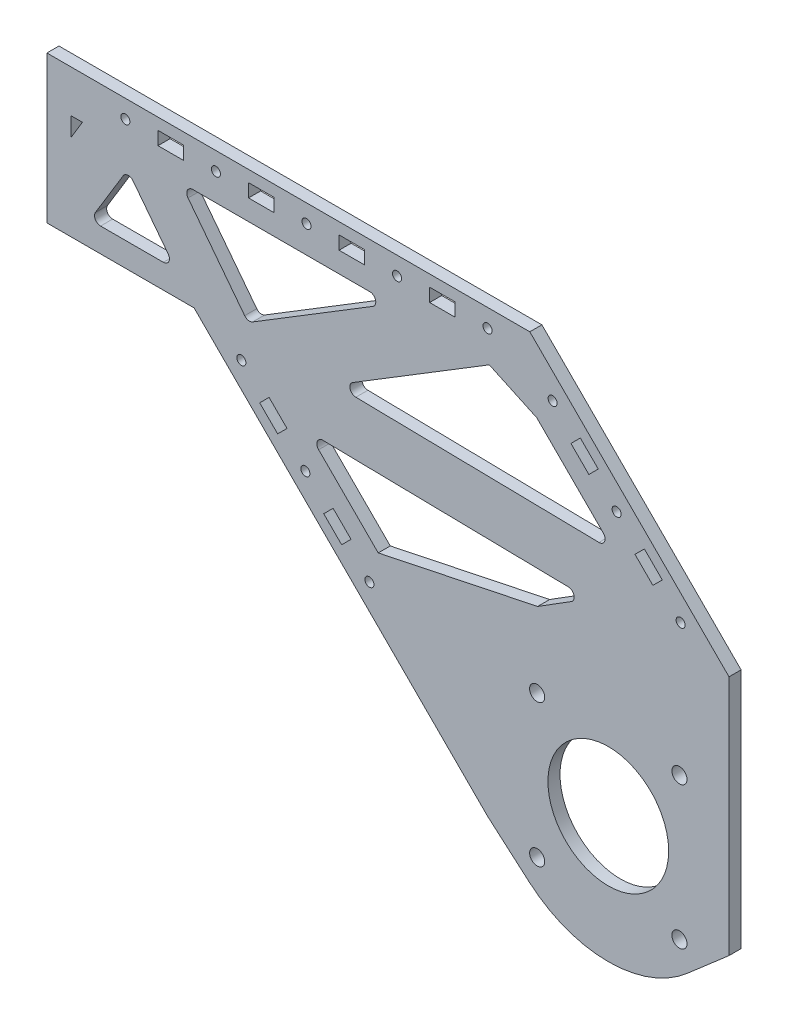
SolidWorks part; units mm, degrees
ref_plane "前视基准面" through (0, 0, 0) normal (0, 0, 1) x (1, 0, 0)
ref_plane "上视基准面" through (0, 0, 0) normal (0, 1, 0) x (1, 0, 0)
ref_plane "右视基准面" through (0, 0, 0) normal (1, 0, 0) x (0, 0, -1)
sketch "草图1" plane through (0, 0, 0) normal (0, 0, 1) x (1, 0, 0)
  line L261 (47.0274, 35.0547) -> (47.0274, 15.0547) construction
  line L315 (7.0274, -4.9453) -> (20.8147, -16.9066)
  line L316 (-52.9726, 135.0547) -> (-52.9726, 126.7057) construction
  line L332 (-112.9726, 135.0547) -> (-97.9726, 135.0547) construction
  line L334 (-42.1726, 137.2547) -> (-33.7726, 137.2547)
  line L335 (-42.1726, 137.2547) -> (-42.1726, 132.8547)
  line L336 (-42.1726, 132.8547) -> (-33.7726, 132.8547)
  line L337 (-33.7726, 137.2547) -> (-33.7726, 132.8547)
  line L338 (-42.1726, 137.2547) -> (-33.7726, 132.8547) construction
  line L339 (-42.1726, 132.8547) -> (-33.7726, 137.2547) construction
  line L389 (-138.9726, 141.0547) -> (21.0274, 141.0547)
  line L390 (-22.9726, 135.0547) -> (-22.9726, 144.5851) construction
  line L395 (-37.9726, 135.0547) -> (-7.9726, 135.0547) construction
  line L418 (87.0274, 75.0547) -> (21.0274, 141.0547)
  line L419 (-3.7726, 132.8547) -> (-12.1726, 137.2547) construction
  line L420 (-3.7726, 137.2547) -> (-12.1726, 132.8547) construction
  line L421 (7.0274, 135.0547) -> (-7.9726, 135.0547) construction
  line L422 (-12.1726, 137.2547) -> (-12.1726, 132.8547)
  line L423 (-3.7726, 132.8547) -> (-12.1726, 132.8547)
  line L424 (-3.7726, 137.2547) -> (-3.7726, 132.8547)
  line L443 (-3.7726, 137.2547) -> (-12.1726, 137.2547)
  line L444 (-102.1726, 137.2547) -> (-93.7726, 132.8547) construction
  line L445 (-102.1726, 132.8547) -> (-93.7726, 137.2547) construction
  line L446 (7.0274, -4.9453) -> (-138.9726, 141.0547) construction
  line L447 (-67.9726, 135.0547) -> (-97.9726, 135.0547) construction
  line L448 (47.0274, 15.0547) -> (7.0274, -54.2273) construction
  line L449 (-63.7726, 132.8547) -> (-72.1726, 137.2547) construction
  line L483 (-63.7726, 137.2547) -> (-72.1726, 132.8547) construction
  line L515 (47.0274, 35.0547) -> (47.0274, 135.0547) construction
  line L516 (47.0274, 135.0547) -> (-52.9726, 135.0547) construction
  line L517 (-102.1726, 137.2547) -> (-93.7726, 137.2547)
  line L518 (-102.1726, 137.2547) -> (-102.1726, 132.8547)
  line L519 (-102.1726, 132.8547) -> (-93.7726, 132.8547)
  line L520 (-93.7726, 137.2547) -> (-93.7726, 132.8547)
  line L521 (-72.1726, 137.2547) -> (-72.1726, 132.8547)
  line L522 (-63.7726, 132.8547) -> (-72.1726, 132.8547)
  line L523 (-63.7726, 137.2547) -> (-63.7726, 132.8547)
  line L524 (-63.7726, 137.2547) -> (-72.1726, 137.2547)
  line L525 (7.0274, -4.9453) -> (-7.4315, -49.5392) construction
  line L551 (7.0274, -4.9453) -> (87.0274, -4.9453) construction
  line L552 (7.0274, -4.9453) -> (7.0274, 75.0547) construction
  line L553 (7.0274, 75.0547) -> (87.0274, 75.0547) construction
  line L554 (87.0274, -4.9453) -> (87.0274, 75.0547)
  line L555 (87.0274, -4.9453) -> (16.9882, -65.7087) construction
  line L556 (21.4033, 132.1936) -> (81.3921, 72.2048) construction
  line L557 (54.0274, 108.0547) -> (35.0674, 89.0947) construction
  line L558 (43.7037, 113.0045) -> (34.6527, 115.8329) construction
  line L559 (55.8659, 94.6197) -> (61.8056, 88.68)
  line L576 (55.8659, 94.6197) -> (58.9772, 97.731)
  line L577 (58.9772, 97.731) -> (64.9169, 91.7913)
  line L578 (61.8056, 88.68) -> (64.9169, 91.7913)
  line L579 (55.8659, 94.6197) -> (64.9169, 91.7913) construction
  line L580 (58.9772, 97.731) -> (61.8056, 88.68) construction
  line L581 (40.5924, 109.8932) -> (37.764, 118.9442) construction
  line L582 (34.6527, 115.8329) -> (37.764, 118.9442)
  line L583 (43.7037, 113.0045) -> (37.764, 118.9442)
  line L584 (40.5924, 109.8932) -> (43.7037, 113.0045)
  line L585 (40.5924, 109.8932) -> (34.6527, 115.8329)
  line L586 (60.3914, 93.2055) -> (58.8358, 91.6499) construction
  line L587 (39.1782, 114.4187) -> (37.6226, 112.8631) construction
  line L588 (-138.9726, 141.0547) -> (-138.9726, 92.2861)
  line L589 (14.0274, 68.0547) -> (9.4285, 72.6537) construction
  line L594 (73.2401, -16.9066) -> (87.0274, -4.9453)
  line L605 (-25.9726, 28.0547) -> (-21.7299, 32.2974) construction
  line L606 (-138.9726, 92.2861) -> (-90.2039, 92.2861)
  line L607 (-81.7187, 92.2861) -> (-21.7299, 32.2974) construction
  line L608 (-90.2039, 92.2861) -> (7.0274, -4.9453)
  line L609 (-59.4183, 73.097) -> (-68.4693, 75.9255) construction
  line L610 (-47.2561, 54.7123) -> (-41.3164, 48.7726)
  line L611 (-47.2561, 54.7123) -> (-44.1448, 57.8235)
  line L612 (-44.1448, 57.8235) -> (-38.2051, 51.8838)
  line L613 (-41.3164, 48.7726) -> (-38.2051, 51.8838)
  line L614 (-47.2561, 54.7123) -> (-38.2051, 51.8838) construction
  line L615 (-44.1448, 57.8235) -> (-41.3164, 48.7726) construction
  line L616 (-62.5296, 69.9858) -> (-65.358, 79.0367) construction
  line L617 (-68.4693, 75.9255) -> (-65.358, 79.0367)
  line L618 (-59.4183, 73.097) -> (-65.358, 79.0367)
  line L619 (-62.5296, 69.9858) -> (-59.4183, 73.097)
  line L620 (-62.5296, 69.9858) -> (-68.4693, 75.9255)
  line L621 (-42.7306, 53.298) -> (-44.2862, 51.7424) construction
  line L622 (-63.9438, 74.5112) -> (-65.4994, 72.9556) construction
  line L623 (47.0274, 15.0547) -> (89.2922, -52.8694) construction
  line L624 (89.2922, -52.8694) -> (7.0274, -54.2273) construction
  circle A39 centre (-52.9726, 135.0547) radius 1.5
  circle A42 centre (47.0274, 15.0547) radius 20
  circle A49 centre (-22.9726, 135.0547) radius 1.5
  circle A69 centre (7.0274, 135.0547) radius 1.5
  circle A92 centre (-112.9726, 135.0547) radius 1.5
  circle A93 centre (-82.9726, 135.0547) radius 1.5
  circle A94 centre (7.0274, -54.2273) radius 5.2 construction
  circle A96 centre (7.0274, -54.2273) radius 15.2 construction
  circle A98 centre (49.7848, 103.8121) radius 1.5
  circle A99 centre (70.998, 82.5989) radius 1.5
  circle A100 centre (28.5716, 125.0253) radius 1.5
  circle A104 centre (-53.3372, 63.9046) radius 1.5
  circle A105 centre (-32.124, 42.6914) radius 1.5
  circle A106 centre (-74.5504, 85.1178) radius 1.5
  circle A107 centre (70.5974, 38.6247) radius 2.5
  circle A108 centre (70.5974, -8.5153) radius 2.5
  circle A109 centre (23.4574, -8.5153) radius 2.5
  circle A110 centre (23.4574, 38.6247) radius 2.5
  arc A111 (73.2401, -16.9066) -> (20.8147, -16.9066) centre (47.0274, 13.3075) cw
  point P5 (210.9534, 218.4629)
  point P6 (288.6284, 218.4629)
  point P54 (-105.4726, 135.0547)
  point P60 (60.3914, 93.2055)
  point P92 (-42.7306, 53.298)
  point P115 (47.0274, -39.6478)
  dimension "D1" = 40
  dimension "D3" = 40
  dimension "D5" = 23.57
  dimension "D4" = 5
  dimension "D6" = 23.57
  dimension "D2" = 40
  dimension "D7" = 60
  dimension "D12" = 3
  dimension "D19" = 10.4
  dimension "D20" = 10
  dimension "D22" = 3
  dimension "D8" = 3
  dimension "D28" = 40
  dimension "D9" = 15
  dimension "D10" = 15
  dimension "D11" = 8.4
  dimension "D13" = 4.4
  dimension "D14" = 6
  dimension "D15" = 45
  dimension "D16" = 15
  dimension "D17" = 8.4
  dimension "D18" = 80
  dimension "D21" = 6
  dimension "D23" = 15
  dimension "D24" = 8.4
  dimension "D25" = 4.4
  dimension "D26" = 4.4
  dimension "D27" = 4
extrude "凸台-拉伸1" add sketch "草图1" along normal blind 4
sketch "草图2" plane through (0, 0, 0) normal (0, 0, -1) x (-1, 0, 0)
  line L0 (74.5504, 85.1178) -> (32.124, 42.6914) construction
  line L3 (-27.0274, 55.0547) -> (-70.998, 82.5989) construction
  line L5 (-7.0274, 135.0547) -> (112.9726, 135.0547) construction
  line L6 (112.9726, 135.0547) -> (138.9726, 92.2861) construction
  line L8 (74.5504, 85.1178) -> (112.9726, 135.0547) construction
  line L9 (138.9726, 92.2861) -> (90.2039, 92.2861) construction
  line L10 (90.2039, 92.2861) -> (74.5504, 85.1178) construction
  line L11 (98.7922, 103.5057) -> (110.419, 118.6169)
  line L12 (113.7131, 118.4362) -> (122.8995, 103.325)
  line L13 (121.1905, 100.2861) -> (100.3774, 100.2861)
  line L14 (52.4384, 75.7338) -> (-40.5172, 74.1251) construction
  line L15 (112.9726, 135.0547) -> (138.9726, 135.0547) construction
  line L16 (138.9726, 141.0547) -> (138.9726, 92.2861) construction
  line L17 (138.9726, 135.0547) -> (138.9726, 92.2861) construction
  line L24 (96.315, 100.2861) -> (112.1978, 120.9288) construction
  line L25 (112.1978, 120.9288) -> (124.7469, 100.2861) construction
  line L26 (127.1982, 127.0547) -> (130.9726, 120.8462)
  line L27 (130.9726, 127.0547) -> (130.9726, 120.8462)
  line L28 (127.1982, 127.0547) -> (130.9726, 127.0547)
  line L29 (74.5504, 85.1178) -> (-7.0274, 135.0547) construction
  line L30 (124.7469, 100.2861) -> (96.315, 100.2861) construction
  line L31 (-23.6122, 63.5354) -> (-40.5172, 74.1251) construction
  line L32 (52.4384, 75.7338) -> (29.2014, 52.4968) construction
  line L33 (-23.3319, 117.5371) -> (-48.886, 91.9829) construction
  line L34 (43.4854, 93.5816) -> (-48.886, 91.9829) construction
  line L35 (43.4854, 93.5816) -> (-7.6073, 124.8574) construction
  line L36 (24.9136, 126.0547) -> (94.6921, 126.0547) construction
  line L37 (72.3501, 97.0171) -> (24.9136, 126.0547) construction
  line L38 (73.4463, 98.4417) -> (92.2149, 122.8351)
  line L39 (32.0116, 126.0547) -> (90.6298, 126.0547)
  line L40 (70.817, 97.9555) -> (30.9675, 122.349)
  line L41 (74.5504, 85.1178) -> (-70.998, 82.5989) construction
  line L42 (-7.0274, 135.0547) -> (-28.5716, 125.0253) construction
  line L43 (-28.5716, 125.0253) -> (-70.998, 82.5989) construction
  line L44 (36.6167, 93.4627) -> (-43.9377, 92.0686)
  line L45 (-23.3319, 117.5371) -> (-45.3865, 95.4825)
  line L46 (-7.6073, 124.8574) -> (-23.3319, 117.5371)
  line L47 (37.6263, 97.1682) -> (-7.6073, 124.8574)
  line L48 (32.124, 42.6914) -> (-27.0274, 55.0547) construction
  line L49 (29.2014, 52.4968) -> (-23.6122, 63.5354)
  line L50 (-23.6122, 63.5354) -> (-34.8054, 70.5471)
  line L51 (47.4901, 75.6482) -> (-33.7783, 74.2417)
  line L52 (48.9389, 72.2343) -> (29.2014, 52.4968)
  line L53 (96.315, 100.2861) -> (96.315, 100.2861) construction
  line L54 (72.3501, 97.0171) -> (94.6921, 126.0547) construction
  arc A2 (110.419, 118.6169) -> (113.7131, 118.4362) centre (112.0041, 117.3973) cw
  arc A3 (98.7922, 103.5057) -> (100.3774, 100.2861) centre (100.3774, 102.2861) ccw
  arc A4 (121.1905, 100.2861) -> (122.8995, 103.325) centre (121.1905, 102.2861) ccw
  arc A6 (-33.7783, 74.2417) -> (-34.8054, 70.5471) centre (-33.7437, 72.242) ccw
  arc A7 (47.4901, 75.6482) -> (48.9389, 72.2343) centre (47.5247, 73.6485) cw
  arc A8 (-45.3865, 95.4825) -> (-43.9377, 92.0686) centre (-43.9723, 94.0683) ccw
  arc A9 (36.6167, 93.4627) -> (37.6263, 97.1682) centre (36.5821, 95.4624) ccw
  arc A10 (32.0116, 126.0547) -> (30.9675, 122.349) centre (32.0116, 124.0547) ccw
  arc A11 (90.6298, 126.0547) -> (92.2149, 122.8351) centre (90.6298, 124.0547) cw
  arc A12 (70.817, 97.9555) -> (73.4463, 98.4417) centre (71.8612, 99.6613) ccw
  dimension "D1" = 8
  dimension "D2" = 8
  dimension "D3" = 9
  dimension "D4" = 9
  dimension "D5" = 9
extrude "切除-拉伸1" cut sketch "草图2" against normal blind 10
